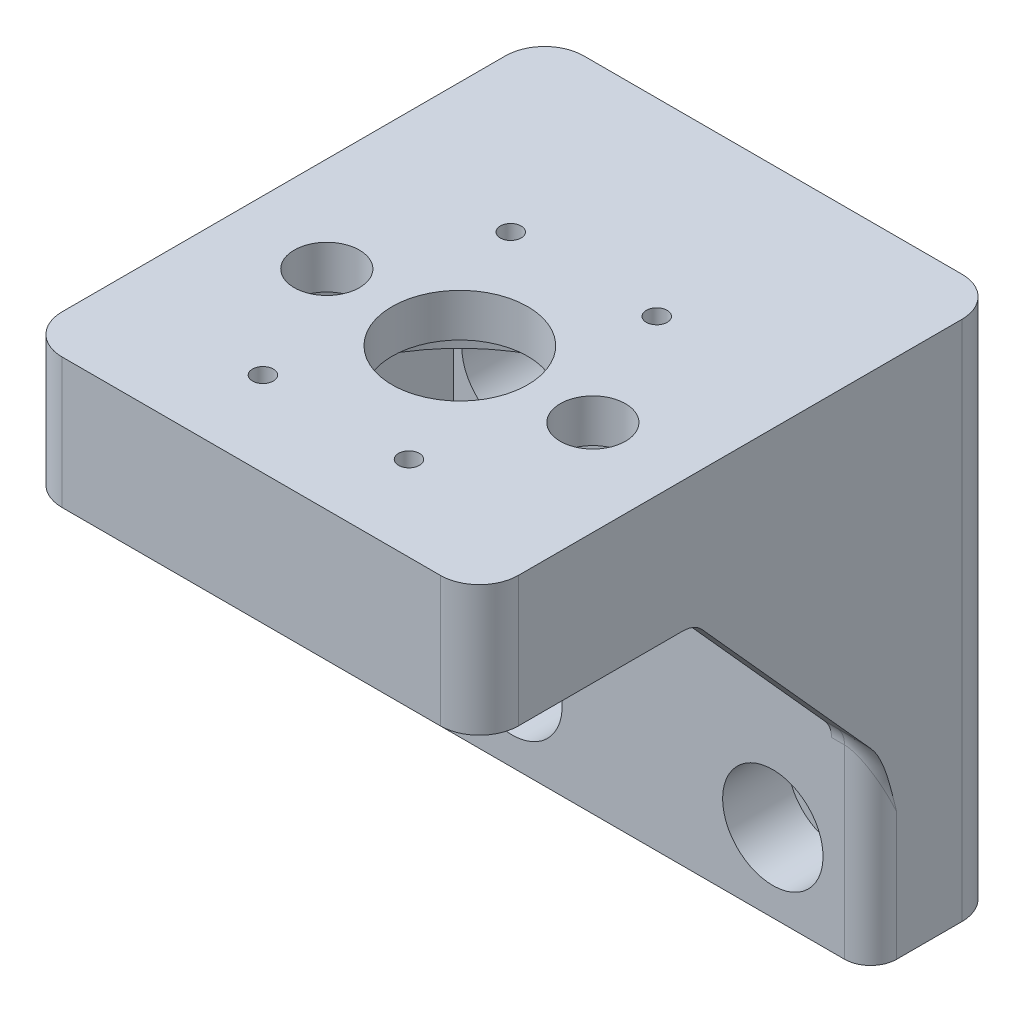
SolidWorks part; units mm, degrees
material "ABS"
ref_plane "Front Plane" through (0, 0, 0) normal (0, 0, 1) x (1, 0, 0)
ref_plane "Top Plane" through (0, 0, 0) normal (0, 1, 0) x (1, 0, 0)
ref_plane "Right Plane" through (0, 0, 0) normal (1, 0, 0) x (0, 0, -1)
sketch "Sketch1" plane through (0, 0, 0) normal (0, 0, 1) x (1, 0, 0)
  line L1 (-22.225, 50.8) -> (22.225, 50.8)
  line L2 (-22.225, 50.8) -> (-22.225, 0)
  line L3 (-22.225, 0) -> (22.225, 0)
  line L4 (22.225, 50.8) -> (22.225, 0)
  dimension "D1" = 44.45
  dimension "D2" = 50.8
extrude "Boss-Extrude1" add sketch "Sketch1" along normal blind 50.8 contours L2 L3 L4 L1
sketch "Sketch2" plane through (0, 0, 0) normal (0, -1, 0) x (1, 0, 0)
  line L0 (-22.225, 0) -> (22.225, 0) construction
  line L1 (0, 30.48) -> (0, 0) construction
  circle A0 centre (0, 30.48) radius 17.653
  dimension "D1" = 35.306
  dimension "D2" = 30.48
extrude "Cut-Extrude1" cut sketch "Sketch2" against normal offset from surface (44.45 mm away) 6.35 up to face at (0, 50.8, 25.4)
sketch "Sketch3" plane through (0, 44.45, 0) normal (0, -1, 0) x (1, 0, 0)
  circle A0 centre (0, 30.48) radius 16.129
  circle A1 centre (0, 30.48) radius 17.653 construction
  dimension "D1" = 32.258
extrude "Cut-Extrude2" cut sketch "Sketch3" against normal blind 2.159
sketch "Sketch4" plane through (0, 46.609, 0) normal (0, -1, 0) x (1, 0, 0)
  line L0 (-7.112, 42.545) -> (7.112, 18.415) construction
  line L1 (-7.112, 42.545) -> (7.112, 42.545) construction
  line L2 (-7.112, 42.545) -> (-7.112, 18.415) construction
  line L3 (-7.112, 18.415) -> (7.112, 18.415) construction
  line L4 (7.112, 42.545) -> (7.112, 18.415) construction
  line L5 (-7.112, 18.415) -> (7.112, 42.545) construction
  line L6 (16.129, 30.48) -> (-16.129, 30.48) construction
  line L7 (0, 18.415) -> (0, 42.545) construction
  circle A0 centre (0, 30.48) radius 6.604
  circle A1 centre (0, 30.48) radius 16.129 construction
  circle A2 centre (-7.112, 42.545) radius 1.016
  circle A3 centre (-7.112, 18.415) radius 1.016
  circle A4 centre (7.112, 18.415) radius 1.016
  circle A5 centre (7.112, 42.545) radius 1.016
  circle A6 centre (-12.954, 30.48) radius 3.175
  circle A7 centre (12.954, 30.48) radius 3.175
  dimension "D1" = 13.208
  dimension "D4" = 2.032
  dimension "D5" = 6.35
  dimension "D2" = 14.224
  dimension "D3" = 24.13
extrude "Cut-Extrude3" cut sketch "Sketch4" against normal through all
sketch "Sketch5" plane through (0, 0, 50.8) normal (0, 0, 1) x (1, 0, 0)
  line L0 (-22.225, 0) -> (22.225, 0) construction
  line L1 (-12.7, 7.62) -> (12.7, 7.62) construction
  line L2 (-12.7, 7.62) -> (-12.7, 33.02) construction
  line L3 (-12.7, 33.02) -> (12.7, 33.02) construction
  line L4 (12.7, 7.62) -> (12.7, 33.02) construction
  line L6 (-12.7, 20.32) -> (-22.225, 20.32) construction
  line L8 (-22.225, 50.8) -> (-22.225, 0) construction
  line L10 (12.7, 20.32) -> (22.225, 20.32) construction
  line L12 (22.225, 50.8) -> (22.225, 0) construction
  circle A0 centre (-12.7, 7.62) radius 4.8895
  circle A1 centre (-12.7, 33.02) radius 4.8895
  circle A2 centre (12.7, 33.02) radius 4.8895
  circle A3 centre (12.7, 7.62) radius 4.8895
  dimension "D3" = 9.779
  dimension "D1" = 25.4
  dimension "D2" = 25.4
  dimension "D4" = 7.62
extrude "Cut-Extrude4" cut sketch "Sketch5" against normal offset from surface (44.45 mm away) 6.35 up to face at (0, 25.4, 0)
sketch "Sketch6" plane through (0, 0, 6.35) normal (0, 0, 1) x (1, 0, 0)
  line L0 (-12.7, 7.62) -> (-12.7, 33.02) construction
  line L1 (-12.7, 33.02) -> (12.7, 33.02) construction
  line L2 (12.7, 33.02) -> (12.7, 7.62) construction
  line L3 (12.7, 7.62) -> (-12.7, 7.62) construction
  circle A0 centre (-12.7, 7.62) radius 3.429
  circle A1 centre (-12.7, 7.62) radius 4.8895 construction
  circle A2 centre (-12.7, 33.02) radius 3.429
  circle A3 centre (12.7, 33.02) radius 3.429
  circle A4 centre (12.7, 7.62) radius 3.429
  dimension "D1" = 6.858
  dimension "D4" = 25.4
  dimension "D5" = 25.4
  dimension "D2" = 2
  dimension "D3" = 2
extrude "Cut-Extrude5" cut sketch "Sketch6" against normal through all
fillet "Fillet1" radius 3.81 4 edges at (-22.225, 25.4, 0) (22.225, 25.4, 0) (-22.225, 25.4, 50.8) (22.225, 25.4, 50.8)
sketch "Sketch7" plane through (0, 0, 0) normal (0, -1, 0) x (1, 0, 0)
  line L0 (22.225, 46.99) -> (22.225, 3.81) construction
  line L1 (-22.225, 50.8) -> (22.225, 50.8)
  line L2 (-22.225, 50.8) -> (-22.225, 12.7)
  line L3 (-22.225, 12.7) -> (22.225, 12.7)
  line L4 (22.225, 50.8) -> (22.225, 12.7)
  line L5 (-18.415, 50.8) -> (18.415, 50.8) construction
  line L6 (-22.225, 46.99) -> (-22.225, 3.81) construction
  line L7 (-18.415, 0) -> (18.415, 0) construction
  dimension "D1" = 12.7
extrude "Cut-Extrude6" cut sketch "Sketch7" against normal offset from surface (38.1 mm away) 12.7 contours L1 L4 L3 L2 up to face at (12.954, 50.8, 33.655)
sketch "Sketch8" plane through (-22.225, 0, 0) normal (-1, 0, 0) x (0, 0, 1)
  line L0 (12.7, 38.1) -> (29.845, 38.1)
  line L1 (46.99, 38.1) -> (12.7, 38.1) construction
  line L2 (29.845, 38.1) -> (12.7, 19.05)
  line L3 (12.7, 38.1) -> (12.7, 0) construction
  line L4 (12.7, 19.05) -> (12.7, 38.1)
extrude "Boss-Extrude2" add sketch "Sketch8" against normal blind 3.81
pattern_linear "LPattern1" count 2 spacing 40.64 along (1, 0, 0) of "Boss-Extrude2"
fillet "Fillet2" radius 2.54 2 edges at (22.225, 9.525, 12.7) (-22.225, 9.525, 12.7)
fillet "Fillet3" radius 2.54 2 edges at (20.32, 38.1, 29.845) (-20.32, 38.1, 29.845)
fillet "Fillet4" radius 2.54 4 edges at (-19.05, 19.05, 12.7) (-21.4811, 18.2234, 11.9561) (21.4811, 18.2234, 11.9561) (19.05, 19.05, 12.7)
